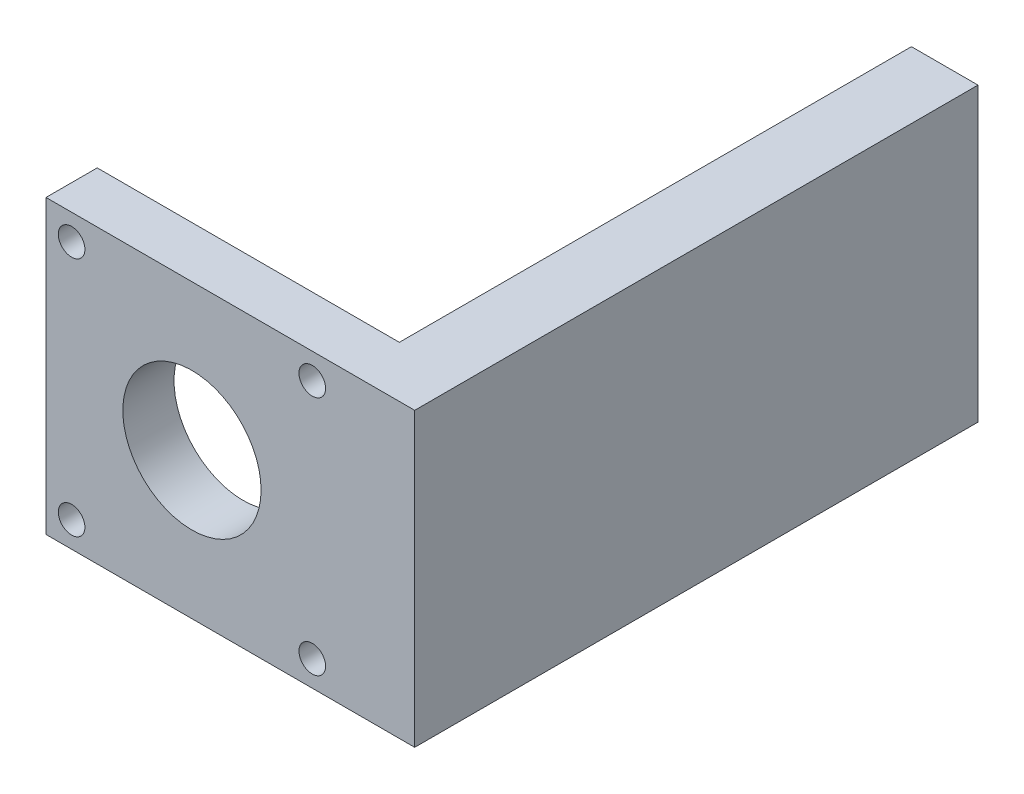
SolidWorks part; units mm, degrees
ref_plane "Front Plane" through (0, 0, 0) normal (0, 0, 1) x (1, 0, 0)
ref_plane "Top Plane" through (0, 0, 0) normal (0, 1, 0) x (1, 0, 0)
ref_plane "Right Plane" through (0, 0, 0) normal (1, 0, 0) x (0, 0, -1)
sketch "Sketch1" plane through (0, 0, 0) normal (0, 0, 1) x (1, 0, 0)
  line L0 (-81.2971, 62) -> (-81.2971, 25.5) construction
  line L1 (-78.2971, 8) -> (-41.7971, 8) construction
  line L2 (-24.2971, 11) -> (-24.2971, 47.5) construction
  line L3 (-27.2971, 65) -> (-63.7971, 65) construction
  line L4 (-81.2971, 62) -> (-81.2971, 25.5)
  line L5 (-78.2971, 8) -> (-41.7971, 8)
  line L6 (-24.2971, 11) -> (-24.2971, 47.5)
  line L7 (-27.2971, 65) -> (-63.7971, 65)
  line L8 (-63.7971, 65) -> (-81.2971, 65)
  line L9 (-81.2971, 65) -> (-81.2971, 62)
  line L10 (-81.2971, 25.5) -> (-81.2971, 8)
  line L11 (-81.2971, 8) -> (-78.2971, 8)
  line L12 (-41.7971, 8) -> (-24.2971, 8)
  line L13 (-24.2971, 8) -> (-24.2971, 11)
  line L14 (-24.2971, 47.5) -> (-24.2971, 65)
  line L15 (-24.2971, 65) -> (-27.2971, 65)
  circle A0 centre (-76.2971, 13) radius 2.6 construction
  circle A1 centre (-29.2971, 13) radius 2.6 construction
  circle A2 centre (-29.2971, 60) radius 2.6 construction
  circle A3 centre (-76.2971, 60) radius 2.6 construction
  circle A4 centre (-76.2971, 13) radius 2.6
  circle A5 centre (-29.2971, 13) radius 2.6
  circle A6 centre (-29.2971, 60) radius 2.6
  circle A7 centre (-76.2971, 60) radius 2.6
extrude "Boss-Extrude1" add sketch "Sketch1" along normal blind 10
sketch "Sketch3" plane through (0, 0, 10) normal (0, 0, 1) x (1, 0, 0)
  circle A2 centre (-52.7971, 36.5) radius 13.5
  circle A3 centre (-52.7971, 36.5) radius 13.5
  dimension "D1" = 1
extrude "Cut-Extrude1" cut sketch "Sketch3" against normal through all
sketch "Sketch4" plane through (0, 0, 10) normal (0, 0, 1) x (1, 0, 0)
  line L0 (-24.2971, 8) -> (-9.2971, 8)
  line L1 (-24.2971, 65) -> (-9.2971, 65)
  line L2 (-9.2971, 65) -> (-9.2971, 8)
  line L3 (-24.2971, 8) -> (-24.2971, 65)
extrude "Boss-Extrude2" add sketch "Sketch4" against normal blind 10
sketch "Sketch5" plane through (0, 0, 0) normal (0, 0, -1) x (-1, 0, 0)
  line L0 (9.2971, 65) -> (9.2971, 8)
  line L1 (9.2971, 8) -> (22.2971, 8)
  line L2 (81.2971, 8) -> (9.2971, 8) construction
  line L3 (22.2971, 8) -> (22.2971, 65)
  line L4 (9.2971, 65) -> (81.2971, 65) construction
  line L5 (22.2971, 65) -> (9.2971, 65)
extrude "Boss-Extrude3" add sketch "Sketch5" along normal blind 100
